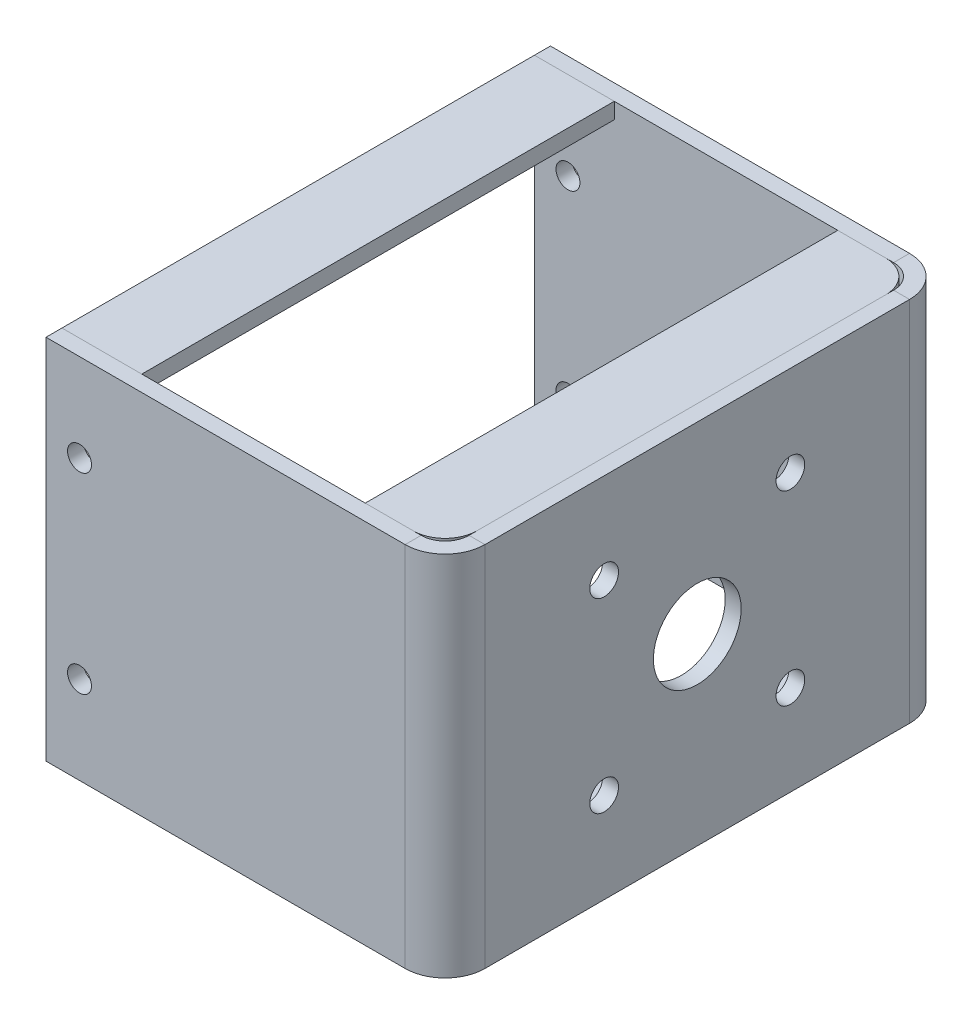
SolidWorks part; units mm, degrees
note: The reader was unsure of these and kept them because the rebuilt part matched: thickness of "Base-Flange1", "Edge-Flange1", "Sheet-Metal1", "Sheet-Metal2", "Sheet-Metal3", "Sheet-Metal4", "Sheet-Metal5", "Sheet-Metal6", "Sheet-Metal7", "Sheet-Metal11"; flange length of "Edge-Flange1".
material "Plain Carbon Steel"
ref_plane "Front Plane" through (0, 0, 0) normal (0, 0, 1) x (1, 0, 0)
ref_plane "Top Plane" through (0, 0, 0) normal (0, 1, 0) x (1, 0, 0)
ref_plane "Right Plane" through (0, 0, 0) normal (1, 0, 0) x (0, 0, -1)
sketch "Sketch1" plane through (0, 0, 0) normal (1, 0, 0) x (0, 0, -1)
  line L1 (-158, -115) -> (158, -115)
  line L2 (-158, -115) -> (-158, 115)
  line L3 (-158, 115) -> (158, 115)
  line L4 (158, -115) -> (158, 115)
  line L5 (-158, -115) -> (158, 115) construction
  line L6 (-158, 115) -> (158, -115) construction
  point P0 (0, 0)
  dimension "D1" = 316
  dimension "D2" = 230
base flange "Base-Flange1" sketch "Sketch1" thickness 10 reverse thickness direction no parameters "D1"=15
edge flange "Edge-Flange1" sketch "Sketch10" flange profiles "Sketch10", "Sketch11" flange angle 90 flange length 250 flange position material inside bend radius 15 thickness 10 relief rectangular parameters "D6"=10, "D8"=1
sketch "Sketch10" plane through (-10, 0, 158) normal (0, 0, 1) x (0, 1, 0)
  line L0 (115, 0) -> (-115, 0) construction
  line L1 (115, 0) -> (-115, 0)
  line L2 (-115, 0) -> (-115, 240)
  line L3 (-115, 240) -> (115, 240)
  line L4 (115, 240) -> (115, 0)
sketch "Sketch11" plane through (-10, 0, -158) normal (0, 0, -1) x (0, -1, 0)
  line L0 (115, 0) -> (-115, 0) construction
  line L1 (115, 0) -> (-115, 0)
  line L2 (-115, 0) -> (-115, 240)
  line L3 (-115, 240) -> (115, 240)
  line L4 (115, 240) -> (115, 0)
bend "EdgeBend1" bend radius 15 bend angle 90 parameters "D5"=1
bend "EdgeBend2" bend radius 15 bend angle 90 parameters "D5"=2
sketch "Sketch12" plane through (0, 0, 0) normal (1, 0, 0) x (0, 0, -1)
  line L0 (-158, -115) -> (158, 115) construction
  circle A0 centre (0, 0) radius 27.5
  dimension "D1" = 55
extrude "Cut-Extrude1" cut sketch "Sketch12" against normal blind 10
sketch "Sketch13" plane through (0, 0, 158) normal (0, 0, 1) x (1, 0, 0)
  line L1 (-250, 115) -> (-250, -115) construction
  circle A0 centre (-229, 60) radius 7.5
  dimension "D1" = 15
  dimension "D2" = 60
  dimension "D3" = 21
extrude "Cut-Extrude2" cut sketch "Sketch13" against normal through all
sketch "Sketch14" plane through (0, 0, 0) normal (1, 0, 0) x (0, 0, -1)
  line L1 (58.3363, -58.3363) -> (-58.3363, -58.3363) construction
  line L2 (58.3363, -58.3363) -> (58.3363, 58.3363) construction
  line L3 (58.3363, 58.3363) -> (-58.3363, 58.3363) construction
  line L4 (-58.3363, -58.3363) -> (-58.3363, 58.3363) construction
  line L5 (58.3363, -58.3363) -> (-58.3363, 58.3363) construction
  line L6 (58.3363, 58.3363) -> (-58.3363, -58.3363) construction
  circle A0 centre (-58.3363, 58.3363) radius 9
  circle A6 centre (0, 0) radius 82.5 construction
  dimension "D1" = 18
  dimension "D2" = 165
extrude "Cut-Extrude3" cut sketch "Sketch14" against normal blind 10
mirror "Mirror1" about plane through (0, 0, 0) normal (0, 1, 0) of "Cut-Extrude2"
sketch "Sketch15" plane through (0, 115, 0) normal (0, 1, 0) x (1, 0, 0)
  line L0 (-250, 148) -> (-25, 148) construction
  line L1 (-60, 148) -> (-30, 148)
  line L2 (-60, 148) -> (-60, -148)
  line L3 (-60, -148) -> (-30, -148)
  line L4 (-10, 128) -> (-10, -128)
  line L5 (-25, -148) -> (-250, -148) construction
  line L6 (-10, 133) -> (-10, -133) construction
  line L8 (-250, 148) -> (-200, 148)
  line L9 (-250, 148) -> (-250, -148)
  line L10 (-250, -148) -> (-200, -148)
  line L11 (-200, 148) -> (-200, -148)
  arc A0 (-30, -148) -> (-10, -128) centre (-30, -128) ccw
  arc A1 (-30, 148) -> (-10, 128) centre (-30, 128) cw
  point P12 (-10, -148)
  dimension "D2" = 20
  dimension "D1" = 50
  dimension "D3" = 50
extrude "Boss-Extrude1" add sketch "Sketch15" against normal blind 10 separate body
mirror "Mirror2" about plane through (0, 0, 0) normal (0, 1, 0) of bodies 107 109
pattern_circular "CirPattern1" count 4 over 360 about axis through (0, 0, 0) along (1, 0, 0) of "Cut-Extrude3" reverse direction yes
sketch "Bend-Lines1" [suppressed] plane through (0, 0, 0) normal (0, 1, 0) x (1, 0, 0)
sketch "Bounding-Box1" [suppressed] plane through (0, 0, 0) normal (0, 1, 0) x (1, 0, 0)
sheet metal parameters "Sheet-Metal1" thickness 10 parameters "D1"=15
flat pattern "Flat-Pattern1" [suppressed]
sketch "Bend-Lines2" plane through (0, 0, 0) normal (0, 1, 0) x (1, 0, 0)
sketch3d "Bounding-Box2" [suppressed]
  line L0 (-162, -100, 0) -> (162, -100, 0) construction
  line L1 (-162, 100, 0) -> (162, 100, 0) construction
  line L2 (-162, -100, 0) -> (-162, 100, 0) construction
  line L3 (162, -100, 0) -> (162, 100, 0) construction
sheet metal parameters "Sheet-Metal2" thickness 10 parameters "D1"=15
flat pattern "Flat-Pattern1"
sketch "Bend-Lines2" plane through (0, 0, 0) normal (1, 0, 0) x (0, 0, -1)
  line L0 (152.708, -100) -> (152.708, 100) construction
  line L1 (-152.708, 100) -> (-152.708, -100) construction
  line L2 (152.708, -100) -> (152.708, 100) construction
  line L3 (-152.708, 100) -> (-152.708, -100) construction
sketch3d "Bounding-Box2" [suppressed]
  line L0 (416.4159, -100, 0) -> (-416.4159, -100, 0) construction
  line L1 (416.4159, 100, 0) -> (-416.4159, 100, 0) construction
  line L2 (416.4159, -100, 0) -> (416.4159, 100, 0) construction
  line L3 (-416.4159, -100, 0) -> (-416.4159, 100, 0) construction
bend of the flat pattern "Flatten-<EdgeBend1>1"
bend of the flat pattern "Flatten-<EdgeBend2>1"
sheet metal parameters "Sheet-Metal3" thickness 10 parameters "D1"=15
flat pattern "Flat-Pattern1"
sketch "Bend-Lines2" plane through (0, 0, 0) normal (1, 0, 0) x (0, 0, -1)
  line L0 (152.708, -100) -> (152.708, 100) construction
  line L1 (-152.708, 100) -> (-152.708, -100) construction
  line L2 (152.708, -100) -> (152.708, 100) construction
  line L3 (-152.708, 100) -> (-152.708, -100) construction
sketch3d "Bounding-Box2" [suppressed]
  line L0 (416.4159, -100, 0) -> (-416.4159, -100, 0) construction
  line L1 (416.4159, 100, 0) -> (-416.4159, 100, 0) construction
  line L2 (416.4159, -100, 0) -> (416.4159, 100, 0) construction
  line L3 (-416.4159, -100, 0) -> (-416.4159, 100, 0) construction
bend of the flat pattern "Flatten-<EdgeBend1>1"
bend of the flat pattern "Flatten-<EdgeBend2>1"
sheet metal parameters "Sheet-Metal4" thickness 10 parameters "D1"=15
flat pattern "Flat-Pattern1"
sketch "Bend-Lines2" plane through (0, 0, 0) normal (1, 0, 0) x (0, 0, -1)
  line L0 (152.708, -100) -> (152.708, 100) construction
  line L1 (-152.708, 100) -> (-152.708, -100) construction
  line L2 (152.708, -100) -> (152.708, 100) construction
  line L3 (-152.708, 100) -> (-152.708, -100) construction
sketch3d "Bounding-Box2" [suppressed]
  line L0 (416.4159, -100, 0) -> (-416.4159, -100, 0) construction
  line L1 (416.4159, 100, 0) -> (-416.4159, 100, 0) construction
  line L2 (416.4159, -100, 0) -> (416.4159, 100, 0) construction
  line L3 (-416.4159, -100, 0) -> (-416.4159, 100, 0) construction
bend of the flat pattern "Flatten-<EdgeBend1>1"
bend of the flat pattern "Flatten-<EdgeBend2>1"
sheet metal parameters "Sheet-Metal5" thickness 10 parameters "D1"=15
flat pattern "Flat-Pattern1"
sketch "Bend-Lines2" plane through (0, 0, 0) normal (1, 0, 0) x (0, 0, -1)
  line L0 (152.708, -100) -> (152.708, 100) construction
  line L1 (-152.708, 100) -> (-152.708, -100) construction
  line L2 (152.708, -100) -> (152.708, 100) construction
  line L3 (-152.708, 100) -> (-152.708, -100) construction
sketch3d "Bounding-Box2" [suppressed]
  line L0 (416.4159, -100, 0) -> (-416.4159, -100, 0) construction
  line L1 (416.4159, 100, 0) -> (-416.4159, 100, 0) construction
  line L2 (416.4159, -100, 0) -> (416.4159, 100, 0) construction
  line L3 (-416.4159, -100, 0) -> (-416.4159, 100, 0) construction
bend of the flat pattern "Flatten-<EdgeBend1>1"
bend of the flat pattern "Flatten-<EdgeBend2>1"
sheet metal parameters "Sheet-Metal6" thickness 10 parameters "D1"=15
flat pattern "Flat-Pattern1"
sketch "Bend-Lines2" plane through (0, 0, 0) normal (1, 0, 0) x (0, 0, -1)
  line L0 (148.708, -115) -> (148.708, 115) construction
  line L1 (-148.708, 115) -> (-148.708, -115) construction
  line L2 (148.708, -115) -> (148.708, 115) construction
  line L3 (-148.708, 115) -> (-148.708, -115) construction
sketch3d "Bounding-Box2" [suppressed]
  line L0 (389.4159, -115, 0) -> (-389.4159, -115, 0) construction
  line L1 (389.4159, 115, 0) -> (-389.4159, 115, 0) construction
  line L2 (389.4159, -115, 0) -> (389.4159, 115, 0) construction
  line L3 (-389.4159, -115, 0) -> (-389.4159, 115, 0) construction
bend of the flat pattern "Flatten-<EdgeBend1>1"
bend of the flat pattern "Flatten-<EdgeBend2>1"
sheet metal parameters "Sheet-Metal7" thickness 10 parameters "D1"=15
flat pattern "Flat-Pattern1"
sketch "Bend-Lines2" plane through (0, 0, 0) normal (1, 0, 0) x (0, 0, -1)
  line L0 (147.9226, -100) -> (147.9226, 100) construction
  line L1 (-147.9226, 100) -> (-147.9226, -100) construction
  line L2 (147.9226, -100) -> (147.9226, 100) construction
  line L3 (-147.9226, 100) -> (-147.9226, -100) construction
sketch3d "Bounding-Box2" [suppressed]
  line L0 (389.8451, -100, 0) -> (-389.8451, -100, 0) construction
  line L1 (389.8451, 100, 0) -> (-389.8451, 100, 0) construction
  line L2 (389.8451, -100, 0) -> (389.8451, 100, 0) construction
  line L3 (-389.8451, -100, 0) -> (-389.8451, 100, 0) construction
bend of the flat pattern "Flatten-<EdgeBend1>1"
bend of the flat pattern "Flatten-<EdgeBend2>1"
sheet metal parameters "Sheet-Metal11" thickness 10 parameters "D1"=15
flat pattern "Flat-Pattern1"
sketch "Bend-Lines2" plane through (0, 0, 0) normal (1, 0, 0) x (0, 0, -1)
  line L0 (148.708, -115) -> (148.708, 115) construction
  line L1 (-148.708, 115) -> (-148.708, -115) construction
  line L2 (148.708, -115) -> (148.708, 115) construction
  line L3 (-148.708, 115) -> (-148.708, -115) construction
sketch3d "Bounding-Box2" [suppressed]
  line L0 (389.4159, -115, 0) -> (-389.4159, -115, 0) construction
  line L1 (389.4159, 115, 0) -> (-389.4159, 115, 0) construction
  line L2 (389.4159, -115, 0) -> (389.4159, 115, 0) construction
  line L3 (-389.4159, -115, 0) -> (-389.4159, 115, 0) construction
bend of the flat pattern "Flatten-<EdgeBend1>1"
bend of the flat pattern "Flatten-<EdgeBend2>1"
